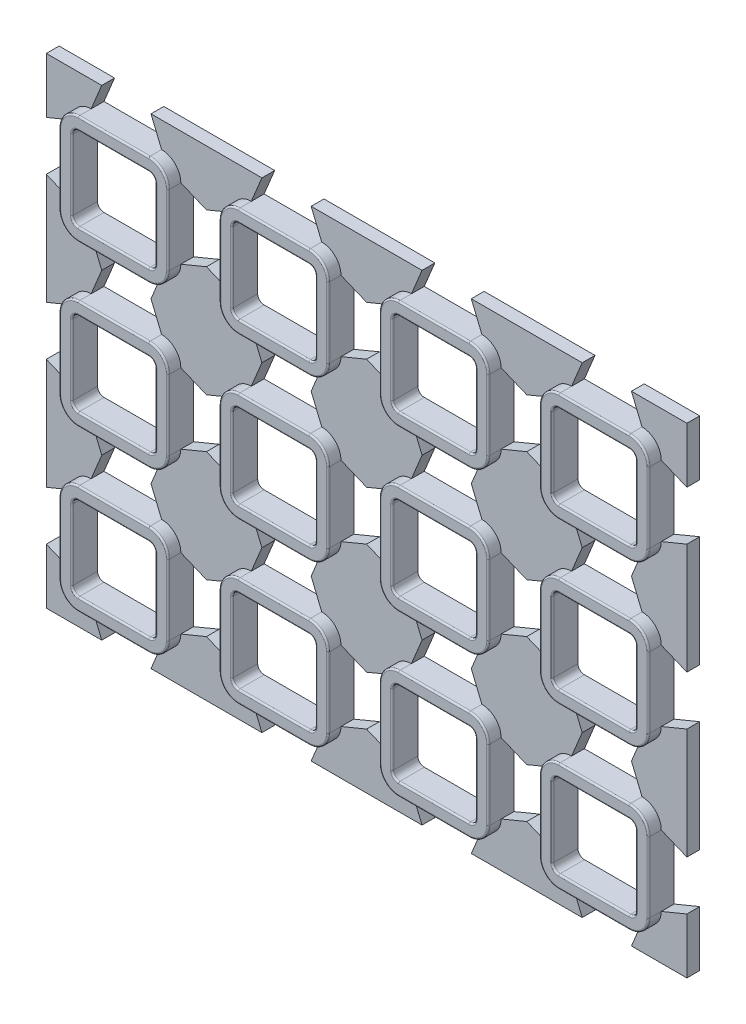
SolidWorks part; units mm, degrees
ref_plane "Ebene vorne" through (0, 0, 0) normal (1, 0, 0) x (0, 1, 0)
ref_plane "Ebene oben" through (0, 0, 0) normal (0, 0, 1) x (0, 1, 0)
ref_plane "Ebene rechts" through (0, 0, 0) normal (0, 1, 0) x (-1, 0, 0)
sketch "Skizze1" plane through (0, 0, 0) normal (0, 0, 1) x (0, 1, 0)
  line L1 (0, 0) -> (75, 0)
  line L2 (0, 0) -> (0, 100)
  line L3 (0, 100) -> (75, 100)
  line L4 (75, 0) -> (75, 100)
  dimension "D1" = 100
  dimension "D2" = 75
extrude "Aufsatz-Linear austragen1" add sketch "Skizze1" along normal blind 2
sketch "Skizze2" plane through (0, 0, 2) normal (0, 0, 1) x (1, 0, 0)
  line L0 (-79, 7) -> (-79, 18)
  line L1 (-100, 0) -> (-75, 0)
  line L2 (-100, 0) -> (-100, 25)
  line L3 (-100, 25) -> (-75, 25)
  line L4 (-75, 0) -> (-75, 25)
  line L5 (-93, 21) -> (-82, 21)
  line L6 (-96, 7) -> (-96, 18)
  line L7 (-93, 4) -> (-82, 4)
  line L8 (-96, 21) -> (-79, 21) construction
  line L9 (-96, 4) -> (-96, 21) construction
  line L10 (-96, 4) -> (-79, 4) construction
  line L11 (-79, 4) -> (-79, 21) construction
  line L12 (-81, 7) -> (-81, 18)
  line L13 (-93, 19) -> (-82, 19)
  line L14 (-94, 7) -> (-94, 18)
  line L15 (-93, 6) -> (-82, 6)
  line L16 (-93, 21) -> (-91.3431, 25)
  line L17 (-96, 18) -> (-100, 16.3431)
  line L18 (-75, 0) -> (-100, 25) construction
  line L19 (-100, 0) -> (-75, 25) construction
  line L20 (-79, 18) -> (-75, 16.3431)
  line L21 (-82, 21) -> (-83.6569, 25)
  line L22 (-82, 4) -> (-83.6569, 0)
  line L23 (-79, 7) -> (-75, 8.6569)
  line L24 (-96, 7) -> (-100, 8.6569)
  line L25 (-93, 4) -> (-91.3431, 0)
  arc A0 (-93, 21) -> (-96, 18) centre (-93, 18) ccw
  arc A1 (-96, 7) -> (-93, 4) centre (-93, 7) ccw
  arc A2 (-79, 7) -> (-82, 4) centre (-82, 7) cw
  arc A3 (-79, 18) -> (-82, 21) centre (-82, 18) ccw
  arc A4 (-81, 18) -> (-82, 19) centre (-82, 18) ccw
  arc A5 (-93, 19) -> (-94, 18) centre (-93, 18) ccw
  arc A6 (-94, 7) -> (-93, 6) centre (-93, 7) ccw
  arc A7 (-81, 7) -> (-82, 6) centre (-82, 7) cw
  point P50 (-87.5, 12.5)
  dimension "D1" = 25
  dimension "D5" = 135
  dimension "D2" = 4
  dimension "D6" = 4
extrude "Schnitt-Linear austragen1" cut sketch "Skizze2" against normal through all contours A7 L12 A4 L13 A5 L14 A6 L15 | L24 L6 L17 L2 | L5 L21 L3 L16 | L0 L23 L4 L20 | L7 L25 L1 L22 region at (-77.1182, 12.5, 2) region at (-87.5, 2.1182, 2) region at (-87.5, 22.8818, 2) region at (-97.8818, 12.5, 2) region at (-87.5, 12.5, 2)
extrude "Aufsatz-Linear austragen2" add sketch "Skizze2<5>" along normal blind 2 contours L0 A3 L5 A0 L6 A1 L7 A2 L12 A7 L15 A6 L14 A5 L13 A4 region at (-80.0487, 5.0487, 2)
sketch "Skizze2<5>" plane through (0, 0, 2) normal (0, 0, 1) x (1, 0, 0) same geometry as "Skizze2"
fillet "Verrundung1" radius 0.25 16 edges at (-81.2929, 18.7071, 4) (-87.5, 19, 4) (-93.7071, 18.7071, 4) (-94, 12.5, 4) (-93.7071, 6.2929, 4) (-87.5, 6, 4) (-81.2929, 6.2929, 4) (-81, 12.5, 4) (-79.8787, 4.8787, 4) (-87.5, 4, 4) (-95.1213, 4.8787, 4) (-96, 12.5, 4) (-95.1213, 20.1213, 4) (-87.5, 21, 4) (-79.8787, 20.1213, 4) (-79, 12.5, 4)
pattern_linear "Lineares Muster1" count 4 spacing 25 along (1, 0, 0) count 3 spacing 25 along (0, 1, 0) of "Aufsatz-Linear austragen2", "Schnitt-Linear austragen1", "Verrundung1"
equation "\"grid­_unit\"= 25mm"
equation "\"grid_columns\" = 4"
equation "\"grid_rows\"= 3"
equation "\"wall_thickness\"= 2mm"
equation "\"D1@Skizze1\"=\"grid­_unit\"*\"grid_columns\""
equation "\"D2@Skizze1\"=\"grid­_unit\"*\"grid_rows\""
equation "\"D1@Aufsatz-Linear austragen1\"=\"wall_thickness\""
equation "\"D2@Skizze2\"=\"wall_thickness\"*2"
equation "\"D3@Skizze2\"=\"wall_thickness\"*1.5"
equation "\"D4@Skizze2\"=\"wall_thickness\""
equation "\"D1@Aufsatz-Linear austragen2\"=\"wall_thickness\""
equation "\"D3@Lineares Muster1\"=\"grid­_unit\""
equation "\"D4@Lineares Muster1\"=\"grid­_unit\""
equation "\"D1@Lineares Muster1\"=\"grid_columns\""
equation "\"D2@Lineares Muster1\"=\"grid_rows\""
equation "\"D1@Verrundung1\"=\"wall_thickness\"/8"
